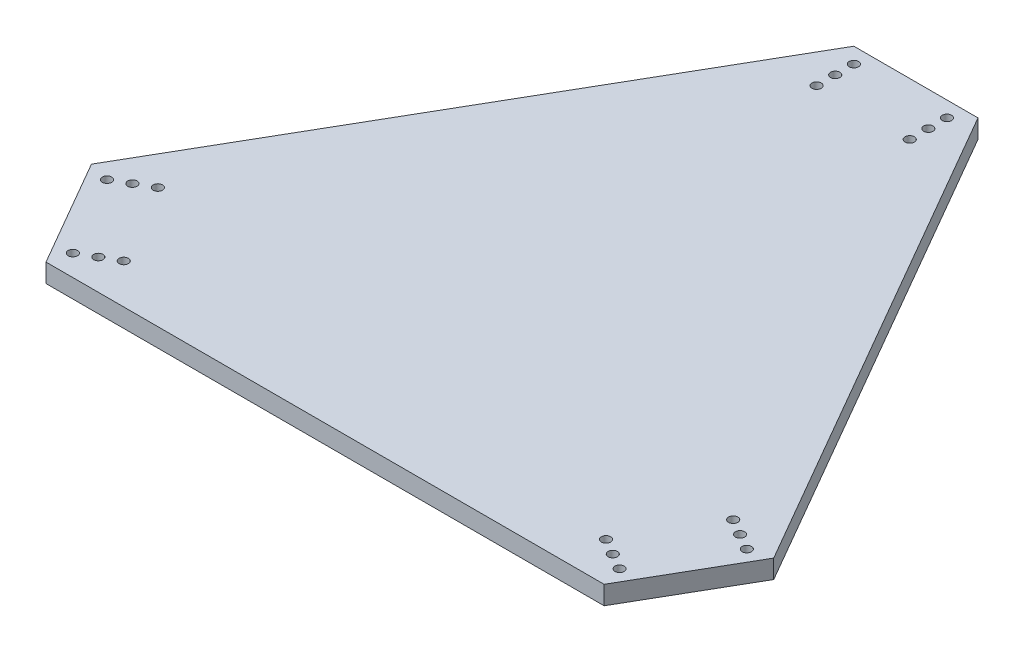
SolidWorks part; units mm, degrees
material "3003 Alloy"
ref_plane "Front Plane" through (0, 0, 0) normal (0, 0, 1) x (1, 0, 0)
ref_plane "Top Plane" through (0, 0, 0) normal (0, 1, 0) x (1, 0, 0)
ref_plane "Right Plane" through (0, 0, 0) normal (1, 0, 0) x (0, 0, -1)
sketch "Sketch8" plane through (0, 0, 0) normal (0, 1, 0) x (1, 0, 0)
  line L0 (-20, 115.359) -> (20, 115.359)
  line L1 (-89.9038, -75) -> (89.9038, -75)
  line L2 (109.9038, -40.359) -> (20, 115.359)
  line L3 (-20, 115.359) -> (-109.9038, -40.359)
  line L4 (109.9038, -40.359) -> (89.9038, -75)
  line L5 (-89.9038, -75) -> (-109.9038, -40.359)
  circle A0 centre (0, 0) radius 150 construction
  point P14 (0, 0)
  point P16 (0, 0)
  dimension "D1" = 3
extrude "Boss-Extrude2" add sketch "Sketch8" along normal blind 6 contours L3 L5 L1 L4 L2 L0
sketch "Sketch9" plane through (0, 6, 0) normal (0, 1, 0) x (1, 0, 0)
  line L0 (-20, 115.359) -> (20, 115.359) construction
  circle A0 centre (15, 110.359) radius 1.5
  circle A1 centre (-15, 110.359) radius 1.5
  circle A2 centre (-15, 104.359) radius 1.5
  circle A3 centre (-15, 98.359) radius 1.5
  circle A4 centre (15, 104.359) radius 1.5
  circle A5 centre (15, 98.359) radius 1.5
  circle A6 centre (88.0737, -68.1699) radius 1.5
  circle A7 centre (103.0737, -42.1891) radius 1.5
  circle A8 centre (97.8775, -39.1891) radius 1.5
  circle A9 centre (92.6814, -36.1891) radius 1.5
  circle A10 centre (82.8775, -65.1699) radius 1.5
  circle A11 centre (77.6814, -62.1699) radius 1.5
  circle A12 centre (-103.0737, -42.1891) radius 1.5
  circle A13 centre (-88.0737, -68.1699) radius 1.5
  circle A14 centre (-82.8775, -65.1699) radius 1.5
  circle A15 centre (-77.6814, -62.1699) radius 1.5
  circle A16 centre (-97.8775, -39.1891) radius 1.5
  circle A17 centre (-92.6814, -36.1891) radius 1.5
  point P40 (0, 0)
  dimension "D1" = 5
  dimension "D2" = 2
  dimension "D3" = 3
  dimension "D4" = 3
extrude "Cut-Extrude1" cut sketch "Sketch9" against normal through all
